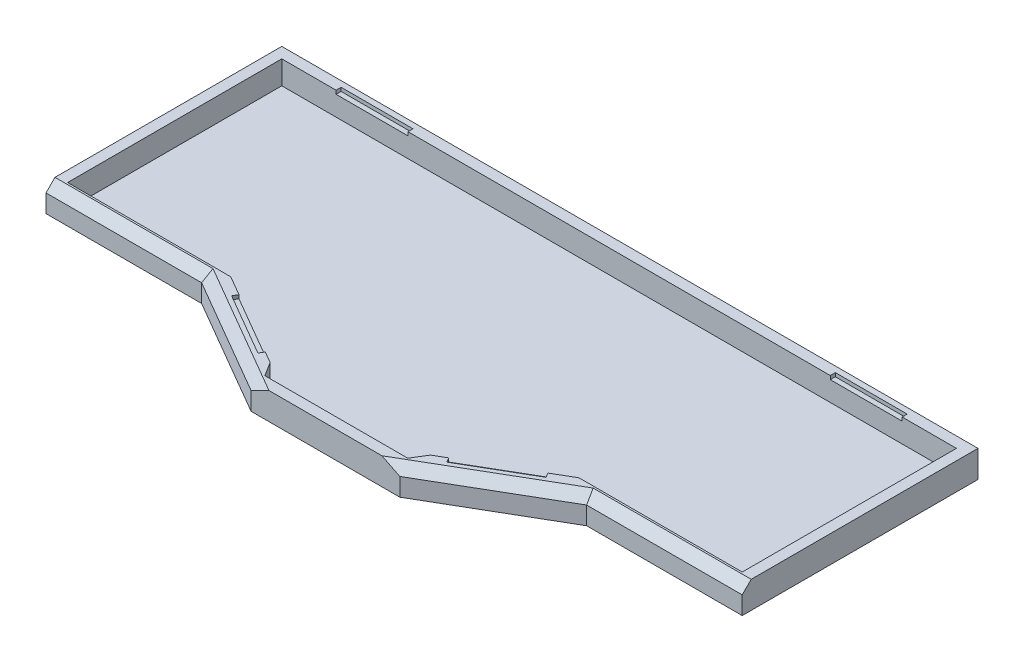
SolidWorks part; units mm, degrees
ref_plane "Front Plane" through (0, 0, 0) normal (0, 0, 1) x (1, 0, 0)
ref_plane "Top Plane" through (0, 0, 0) normal (0, 1, 0) x (1, 0, 0)
ref_plane "Right Plane" through (0, 0, 0) normal (1, 0, 0) x (0, 0, -1)
sketch "Sketch1" plane through (0, 0, 0) normal (0, 1, 0) x (1, 0, 0)
  line L1 (-193.7, 84.7) -> (193.7, 84.7)
  line L2 (-193.7, 84.7) -> (-193.7, -84.7)
  line L3 (-193.7, -84.7) -> (193.7, -84.7)
  line L4 (193.7, 84.7) -> (193.7, -84.7)
  line L5 (-193.7, 84.7) -> (193.7, -84.7) construction
  line L6 (-193.7, -84.7) -> (193.7, 84.7) construction
  point P0 (0, 0)
  dimension "D1" = 387.4
  dimension "D2" = 169.4
extrude "Boss-Extrude1" add sketch "Sketch1" along normal blind 15
sketch "Sketch2" plane through (0, 15, 0) normal (0, 1, 0) x (1, 0, 0)
  line L0 (0, 78.7) -> (0, 84.7) construction
  line L2 (-187.7, 78.7) -> (187.7, 78.7)
  line L3 (-187.7, 78.7) -> (-187.7, -78.7)
  line L4 (-187.7, -78.7) -> (187.7, -78.7)
  line L5 (187.7, 78.7) -> (187.7, -78.7)
  line L6 (-187.7, 78.7) -> (187.7, -78.7) construction
  line L7 (-187.7, -78.7) -> (187.7, 78.7) construction
  line L8 (193.7, 84.7) -> (-193.7, 84.7) construction
  line L9 (187.7, 0) -> (193.7, 0) construction
  line L10 (193.7, -84.7) -> (193.7, 84.7) construction
  point P0 (0, 0)
  dimension "D1" = 6
extrude "Cut-Extrude1" cut sketch "Sketch2" against normal offset from surface (13 mm away) 2 up to face at (0, 0, 0)
sketch "Sketch3" plane through (0, 15, 0) normal (0, 1, 0) x (1, 0, 0)
  line L0 (193.7, 84.7) -> (157.5, 84.7) construction
  line L1 (193.7, 84.7) -> (-193.7, 84.7) construction
  line L2 (157.5, 81.5) -> (157.5, 78.7)
  line L3 (-187.7, 78.7) -> (187.7, 78.7) construction
  line L4 (157.5, 78.7) -> (117.5, 78.7)
  line L5 (187.7, 78.7) -> (-187.7, 78.7) construction
  line L6 (117.5, 78.7) -> (117.5, 81.5)
  line L7 (117.5, 81.5) -> (157.5, 81.5)
  line L8 (157.5, 81.5) -> (157.5, 84.7) construction
  line L9 (-193.7, 84.7) -> (-157.5, 84.7) construction
  line L10 (-157.5, 81.5) -> (-157.5, 78.7)
  line L11 (-157.5, 78.7) -> (-117.5, 78.7)
  line L12 (-117.5, 78.7) -> (-117.5, 81.5)
  line L13 (-117.5, 81.5) -> (-157.5, 81.5)
  line L14 (-157.5, 81.5) -> (-157.5, 84.7) construction
  dimension "D1" = 36.2
  dimension "D2" = 2.8
  dimension "D3" = 40
  dimension "D4" = 36.2
  dimension "D5" = 2.8
  dimension "D6" = 40
extrude "Cut-Extrude2" cut sketch "Sketch3" against normal blind 2
sketch "Sketch4" plane through (0, 2, 0) normal (0, 1, 0) x (1, 0, 0)
  line L0 (187.7, -40.5) -> (105.5, -40.5)
  line L1 (187.7, -78.7) -> (187.7, 78.7) construction
  line L2 (-187.7, -46.5) -> (-107.1167, -46.5)
  line L3 (105.5, -40.5) -> (39.7605, -78.7)
  line L4 (-187.7, -78.7) -> (187.7, -78.7) construction
  line L5 (-107.1167, -46.5) -> (-51.7027, -78.7)
  line L6 (-51.7027, -78.7) -> (-39.7605, -78.7)
  line L7 (-72.6302, -59.6) -> (-75.6447, -64.7878) construction
  line L8 (-39.7605, -78.7) -> (-105.5, -40.5)
  line L9 (-105.5, -40.5) -> (-187.7, -40.5)
  line L10 (-187.7, 78.7) -> (-187.7, -78.7) construction
  line L11 (-187.7, -46.5) -> (-187.7, -40.5)
  line L12 (-187.7, -40.5) -> (-187.7, -78.7) construction
  line L13 (-187.7, -78.7) -> (-39.7605, -78.7) construction
  line L14 (39.7605, -78.7) -> (187.7, -78.7) construction
  line L15 (187.7, -78.7) -> (187.7, -40.5) construction
  line L16 (79.4097, -62.6) -> (76.3952, -57.4122) construction
  line L19 (187.7, -40.5) -> (187.7, -46.5)
  line L20 (187.7, -46.5) -> (107.1167, -46.5)
  line L21 (107.1167, -46.5) -> (51.7027, -78.7)
  line L22 (51.7027, -78.7) -> (39.7605, -78.7)
  dimension "D1" = 38.2
  dimension "D2" = 82.2
  dimension "D3" = 147.9395
  dimension "D4" = 6
  dimension "D5" = 6
extrude "Boss-Extrude2" add sketch "Sketch4" along normal up to surface (13 mm away) up to face at (0, 15, -53.4)
sketch "Sketch5" plane through (0, 0, 0) normal (0, -1, 0) x (1, 0, 0)
  line L0 (107.1167, 46.5) -> (193.7, 46.5)
  line L1 (193.7, 84.7) -> (193.7, -84.7) construction
  line L2 (193.7, 46.5) -> (193.7, 84.7)
  line L4 (-193.7, 84.7) -> (-193.7, 46.5)
  line L5 (-193.7, -84.7) -> (-193.7, 84.7) construction
  line L6 (-193.7, 46.5) -> (-107.1167, 46.5)
  line L7 (-107.1167, 46.5) -> (-51.7027, 78.7)
  line L8 (-51.7027, 78.7) -> (-41.3771, 84.7)
  line L10 (41.3771, 84.7) -> (51.7027, 78.7)
  line L11 (51.7027, 78.7) -> (107.1167, 46.5)
  line L12 (-41.3771, 84.7) -> (-193.7, 84.7)
  line L13 (41.3771, 84.7) -> (193.7, 84.7)
extrude "Cut-Extrude3" cut sketch "Sketch5" against normal through all
chamfer "Chamfer1" distance 5 angle 45 4 edges at (150.4083, 15, 46.5) (74.2469, 15, 65.6) (-74.2469, 15, 65.6) (-150.4083, 15, 46.5)
sketch "Sketch7" plane through (-44.224, 0, 76.1063) normal (0.5024, 0, -0.8646) x (-0.8646, 0, -0.5024)
  line L0 (70.8701, 2) -> (70.8701, 15)
  line L1 (70.8701, 15) -> (-5.1623, 15)
  line L2 (-5.1623, 15) -> (-5.1623, 2)
  line L3 (-5.1623, 2) -> (70.8701, 2)
extrude "Boss-Extrude3" add sketch "Sketch7" along normal blind 4.3231
chamfer "Chamfer3" distance 4.3231 angle 62 1 edges at (-37.5884, 8.5, 74.9621) first distance on face at (-38.6745, 8.5, 76.8311)
chamfer "Chamfer4" distance 4.3231 angle 60 1 edges at (-103.328, 8.5, 36.7621) first distance on face at (-104.414, 8.5, 38.6311)
sketch "Sketch8" plane through (44.224, 0, 76.1063) normal (-0.5024, 0, -0.8646) x (-0.8646, 0, 0.5024)
  line L0 (5.1623, 2) -> (5.1623, 15)
  line L1 (5.1623, 15) -> (-70.8701, 15)
  line L2 (-70.8701, 15) -> (-70.8701, 2)
  line L3 (-70.8701, 2) -> (5.1623, 2)
extrude "Boss-Extrude4" add sketch "Sketch8" along normal blind 4.3231
chamfer "Chamfer5" distance 4.3231 angle 62 1 edges at (37.5884, 8.5, 74.9621) first distance on face at (38.6745, 8.5, 76.8311)
chamfer "Chamfer6" distance 4.3231 angle 60 1 edges at (103.328, 8.5, 36.7621) first distance on face at (104.414, 8.5, 38.6311)
sketch "Sketch9" plane through (0, 15, 0) normal (0, 1, 0) x (1, 0, 0)
  line L0 (70.0073, -59.5939) -> (87.4727, -49.445)
  line L2 (87.2998, -49.5455) -> (52.7147, -69.6422) construction
  line L3 (87.4727, -49.445) -> (85.9654, -46.8512)
  line L4 (44.6184, -70.8772) -> (96.8538, -40.5242) construction
  line L5 (85.9654, -46.8512) -> (51.0346, -67.1488)
  line L6 (51.0346, -67.1488) -> (52.5418, -69.7427)
  line L7 (52.5418, -69.7427) -> (70.0073, -59.5939)
  line L8 (-70.0073, -59.5939) -> (-87.4727, -49.445)
  line L9 (-52.7147, -69.6422) -> (-87.2998, -49.5455) construction
  line L10 (-87.4727, -49.445) -> (-85.9654, -46.8512)
  line L11 (-96.8538, -40.5242) -> (-44.6184, -70.8772) construction
  line L12 (-85.9654, -46.8512) -> (-51.0346, -67.1488)
  line L13 (-51.0346, -67.1488) -> (-52.5418, -69.7427)
  line L14 (-52.5418, -69.7427) -> (-70.0073, -59.5939)
  dimension "D1" = 40.4
  dimension "D2" = 40.4
extrude "Cut-Extrude4" cut sketch "Sketch9" against normal blind 2
equation "\"full_width\"=375"
equation "\"D1@Sketch1\"=\"full_width\"+(\"added_width\"*2)+(\"margin1\"*2)"
equation "\"added_width\"=6"
equation "\"full_height\"= 157"
equation "\"D2@Sketch1\"=\"full_height\"+(\"added_height\"*2)+(\"margin1\"*2)"
equation "\"added_height\"=6"
equation "\"D1@Sketch3\"=30.00mm+\"added_width\"+\"margin1\""
equation "\"tab_depth\" = 3"
equation "\"D2@Sketch3\"=\"tab_depth\"-\"margin1\""
equation "\"tab_width\"=40"
equation "\"D3@Sketch3\"=\"tab_width\""
equation "\"tab_height\"=2"
equation "\"D1@Cut-Extrude2\"=\"tab_height\""
equation "\"D4@Sketch3\"=30mm+\"added_width\"+\"margin1\""
equation "\"D5@Sketch3\"=\"tab_depth\"-\"margin1\""
equation "\"D6@Sketch3\"=\"tab_width\""
equation "\"D2@Sketch2\"=\"added_height\""
equation "\"D1@Sketch2\"=\"added_width\""
equation "\"margin1\"= 0.2"
equation "\"D2@Chamfer5\"=90deg-28deg"
equation "\"D2@Chamfer3\"=90deg-28deg"
equation "\"D1@Sketch9\"=\"tab_width\"+(\"margin1\" *2)"
equation "\"D1@Cut-Extrude4\"=\"tab_height\""
equation "\"D2@Sketch9\"=\"tab_width\"+(\"margin1\"*2)"
